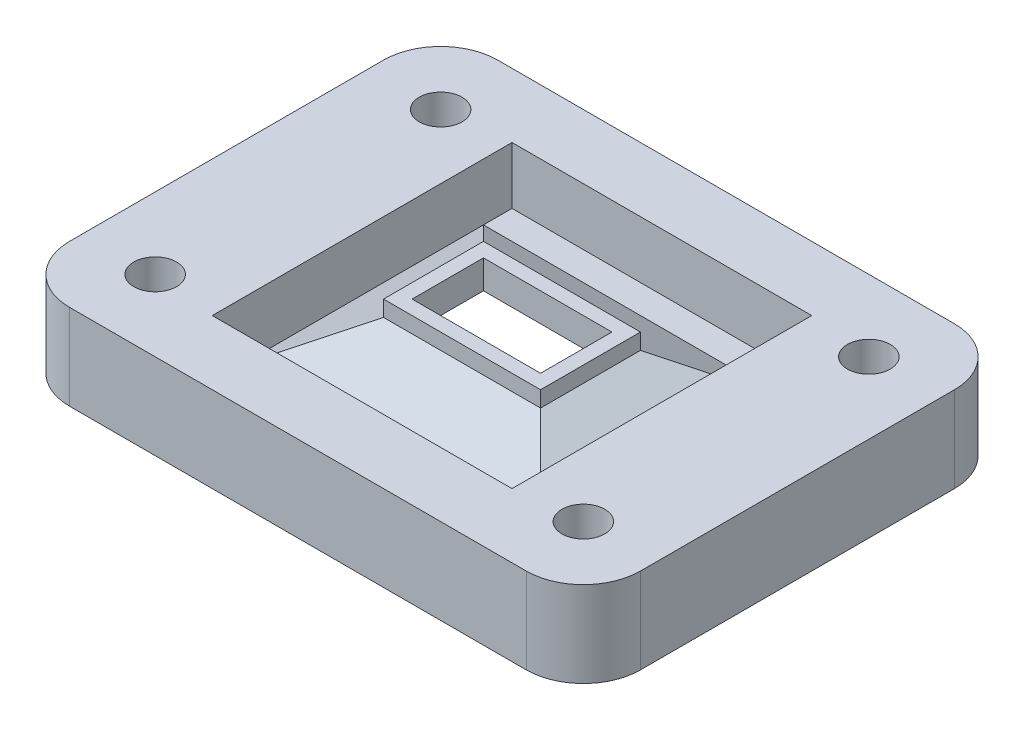
SolidWorks part; units mm, degrees
ref_plane "Front" through (0, 0, 0) normal (0, 0, 1) x (1, 0, 0)
ref_plane "Top" through (0, 0, 0) normal (0, 1, 0) x (1, 0, 0)
ref_plane "Right" through (0, 0, 0) normal (1, 0, 0) x (0, 0, -1)
sketch "Sketch1" plane through (0, 0, 0) normal (0, 1, 0) x (1, 0, 0)
  line L1 (0, 0) -> (40, 0)
  line L2 (0, 0) -> (0, 30)
  line L3 (0, 30) -> (40, 30)
  line L4 (40, 0) -> (40, 30)
  dimension "D1" = 40
  dimension "D2" = 30
extrude "Boss-Extrude1" add sketch "Sketch1" along normal blind 6
sketch "Sketch2" plane through (0, 6, 0) normal (0, 1, 0) x (1, 0, 0)
  line L0 (20, 30) -> (20, 0) construction
  line L1 (40, 30) -> (0, 30) construction
  line L2 (0, 0) -> (40, 0) construction
  line L3 (0, 15) -> (40, 15) construction
  line L4 (0, 30) -> (0, 0) construction
  line L5 (40, 0) -> (40, 30) construction
  circle A0 centre (5, 5) radius 1.5
  circle A1 centre (5, 25) radius 1.5
  circle A2 centre (35, 5) radius 1.5
  circle A3 centre (35, 25) radius 1.5
  dimension "D1" = 3
  dimension "D2" = 5
  dimension "D3" = 5
extrude "Cut-Extrude1" cut sketch "Sketch2" against normal up to surface (6 mm away) up to face at (20, 0, -15)
fillet "Fillet1" radius 4 4 edges at (0, 3, -30) (40, 3, -30) (40, 3, 0) (0, 3, 0)
sketch "Sketch3" plane through (0, 6, 0) normal (0, 1, 0) x (1, 0, 0)
  line L0 (4, 0) -> (36, 0) construction
  line L1 (9.5, 4.5) -> (30.5, 4.5)
  line L2 (9.5, 4.5) -> (9.5, 25.5)
  line L3 (9.5, 25.5) -> (30.5, 25.5)
  line L4 (30.5, 4.5) -> (30.5, 25.5)
  line L5 (0, 26) -> (0, 4) construction
  point P4 (20, 4.5)
  point P7 (20, 0)
  point P8 (9.5, 15)
  point P11 (0, 15)
  dimension "D1" = 21
  dimension "D2" = 21
extrude "Cut-Extrude2" cut sketch "Sketch3" against normal blind 4
sketch "Sketch6" plane through (0, 2, 0) normal (0, 1, 0) x (1, 0, 0)
  line L0 (9.5, 25.5) -> (9.5, 4.5) construction
  line L1 (15.5, 12.5) -> (24.5, 12.5)
  line L2 (15.5, 12.5) -> (15.5, 17.5)
  line L3 (15.5, 17.5) -> (24.5, 17.5)
  line L4 (24.5, 12.5) -> (24.5, 17.5)
  line L5 (30.5, 25.5) -> (9.5, 25.5) construction
  line L6 (30.5, 4.5) -> (30.5, 25.5) construction
  line L7 (9.5, 4.5) -> (30.5, 4.5) construction
  dimension "D1" = 6
  dimension "D2" = 6
  dimension "D3" = 8
  dimension "D4" = 8
extrude "Cut-Extrude3" cut sketch "Sketch6" against normal up to surface (2 mm away) up to face at (5, 0, -26.5)
sketch "Sketch7" plane through (0, 2, 0) normal (0, 1, 0) x (1, 0, 0)
  line L5 (15.5, 17.5) -> (24.5, 17.5)
  line L6 (15.5, 17.5) -> (15.5, 12.5)
  line L7 (15.5, 12.5) -> (24.5, 12.5)
  line L8 (14.5, 11.5) -> (25.5, 11.5)
  line L9 (25.5, 11.5) -> (25.5, 18.5)
  line L10 (25.5, 18.5) -> (14.5, 18.5)
  line L11 (14.5, 18.5) -> (14.5, 11.5)
  line L12 (14.5, 11.5) -> (25.5, 11.5)
  line L13 (25.5, 11.5) -> (25.5, 18.5)
  line L14 (25.5, 18.5) -> (14.5, 18.5)
  line L15 (14.5, 18.5) -> (14.5, 11.5)
  line L16 (24.5, 17.5) -> (24.5, 12.5)
  dimension "D1" = 1
extrude "Boss-Extrude2" add sketch "Sketch7" along normal blind 4
chamfer "Chamfer1" distance 4 angle 60 4 edges at (15.5, 0, -15) (20, 0, -12.5) (24.5, 0, -15) (20, 0, -17.5) first distance on face at (15.5, 3, -15) first distance on face at (20, 3, -12.5) first distance on face at (24.5, 3, -15) first distance on face at (20, 3, -17.5)
chamfer "Chamfer2" distance 5 angle 30 4 edges at (14.5, 2, -15) (20, 2, -18.5) (25.5, 2, -15) (20, 2, -11.5) first distance on face at (20, 2, -15)
